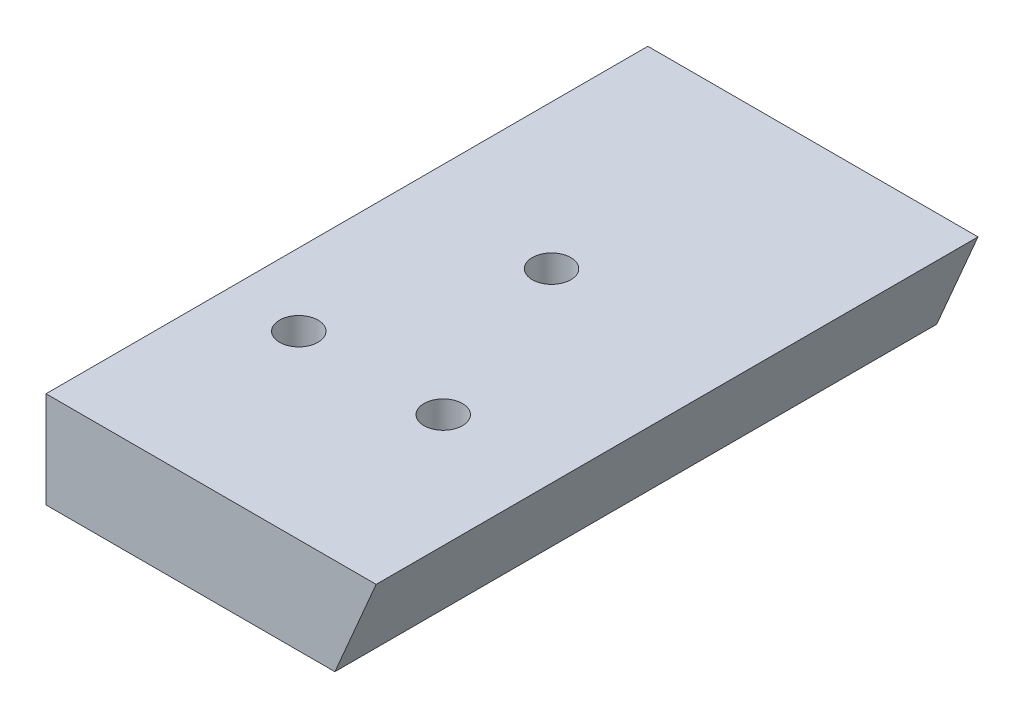
SolidWorks part; units mm, degrees
ref_plane "Alzado" through (0, 0, 0) normal (0, 0, 1) x (1, 0, 0)
ref_plane "Planta" through (0, 0, 0) normal (0, 1, 0) x (1, 0, 0)
ref_plane "Vista lateral" through (0, 0, 0) normal (1, 0, 0) x (0, 0, -1)
sketch "Croquis1" plane through (0, 0, 0) normal (0, 0, 1) x (1, 0, 0)
  line L1 (69.7615, 72.3249) -> (-69.7615, 72.3249) construction
  line L2 (45.7615, 80.3249) -> (73.1901, 80.3249)
  line L4 (45.7615, 72.3249) -> (69.7615, 72.3249)
  line L6 (45.7615, 80.3249) -> (45.7615, 72.3249)
  line L9 (73.1901, 80.3249) -> (69.7615, 72.3249)
  line L11 (94, 128.8813) -> (69.7615, 72.3249) construction
  dimension "D2" = 8
  dimension "D1" = 24
  dimension "D3" = 27.4286
extrude "Saliente-Extruir1" add sketch "Croquis1" along normal up to surface (50 mm away)
sketch "Croquis3" plane through (0, 72.3249, 0) normal (0, -1, 0) x (1, 0, 0)
  line L0 (69.7615, 100) -> (69.7615, 0) construction
  line L1 (69.7615, 100) -> (69.7615, 0)
  line L2 (57.7615, 50) -> (57.7615, 0) construction
  line L3 (45.7615, 50) -> (69.7615, 50) construction
  line L4 (45.7615, 0) -> (69.7615, 0) construction
  line L5 (45.7615, 25) -> (69.7615, 25) construction
  line L7 (45.7615, 50) -> (45.7615, 0) construction
  circle A0 centre (63.7615, 35) radius 1.6
  circle A1 centre (57.7615, 20) radius 1.6
  circle A3 centre (51.7615, 35) radius 1.6
  dimension "D2" = 3.2
  dimension "D1" = 12
  dimension "D3" = 15
  dimension "D6" = 15
  dimension "D7" = 6
extrude "Cortar-Extruir1" cut sketch "Croquis3" against normal up to next contours A3 | A0 | L2 A1 | A1 L2 region at (63.7615, 72.3249, 35) region at (57.7615, 72.3249, 20) region at (51.7615, 72.3249, 35)
ref_plane "Plano1" through (45.7615, 0, 0) normal (-1, 0, 0) x (0, 0, 1)
sketch "Croquis6" plane through (0, 0, 0) normal (0, 0, -1) x (-1, 0, 0)
  line L0 (-73.1901, 80.3249) -> (-73.1901, 72.3249) construction
  line L1 (-73.1901, 76.3249) -> (-45.7615, 76.3249) construction
  line L2 (-59.4758, 80.3249) -> (-59.4758, 72.3249) construction
  line L3 (-59.4758, 72.3249) -> (-73.1901, 80.3249) construction
  line L4 (-73.1901, 80.3249) -> (-69.7615, 72.3249)
  line L5 (-69.7615, 72.3249) -> (-45.7615, 72.3249)
  line L6 (-45.7615, 72.3249) -> (-45.7615, 80.3249)
  line L7 (-45.7615, 80.3249) -> (-73.1901, 80.3249)
  line L9 (-69.7615, 72.3249) -> (-45.7615, 72.3249)
  line L10 (-45.7615, 72.3249) -> (-45.7615, 80.3249)
  line L11 (-45.7615, 80.3249) -> (-73.1901, 80.3249)
  line L12 (-59.4758, 80.3249) -> (-73.1901, 72.3249) construction
  line L17 (-73.1901, 80.3249) -> (-69.7615, 72.3249)
  circle A0 centre (-66.333, 76.3249) radius 1.9
  circle A2 centre (-52.6187, 76.3249) radius 1.9
  dimension "D2" = 3.8
  dimension "D1" = 0
extrude "Cortar-Extruir3" cut sketch "Croquis6" against normal blind 10 contours A0 | A2
